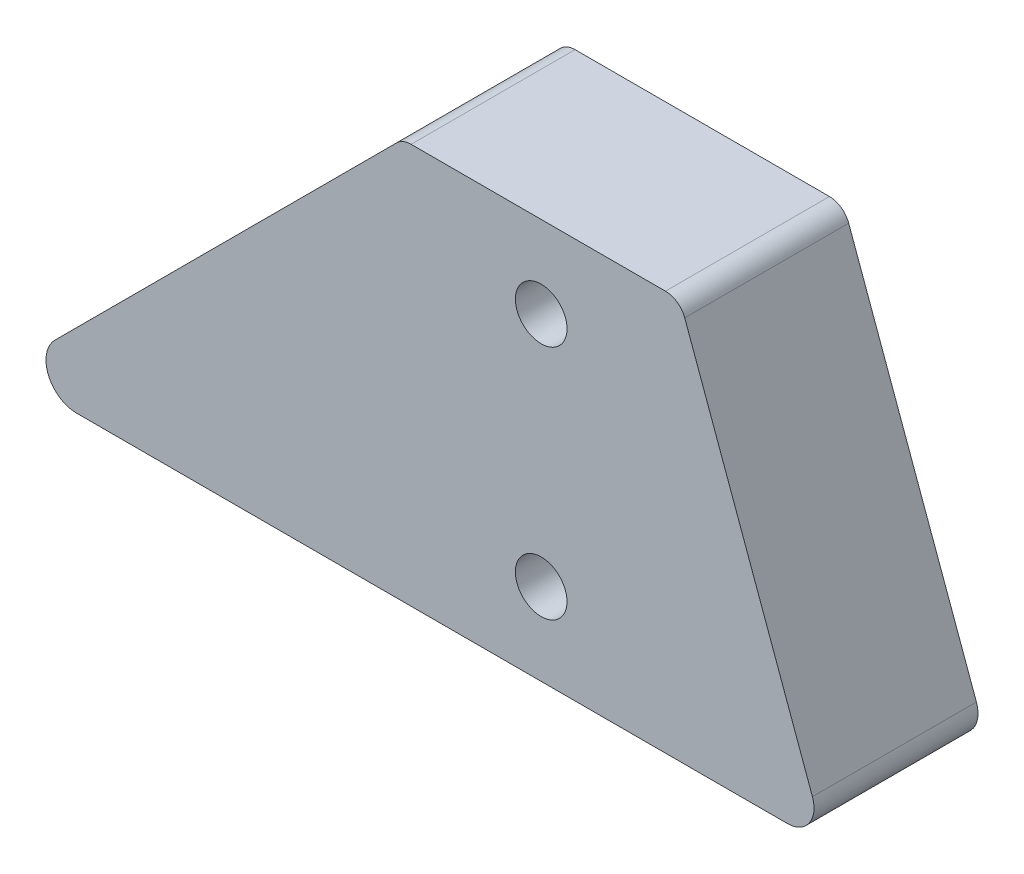
SolidWorks part; units mm, degrees
material "6061 Alloy"
ref_plane "Front Plane" through (0, 0, 0) normal (0, 0, 1) x (1, 0, 0)
ref_plane "Top Plane" through (0, 0, 0) normal (0, 1, 0) x (1, 0, 0)
ref_plane "Right Plane" through (0, 0, 0) normal (1, 0, 0) x (0, 0, -1)
sketch "Sketch1" plane through (0, 0, 0) normal (0, 0, 1) x (1, 0, 0)
  line L3 (9.525, 52.6) -> (-38.1, 52.6)
  line L5 (-38.1, 52.6) -> (-38.1, -45)
  line L6 (-38.1, -45) -> (9.525, -45)
  line L7 (9.525, 52.6) -> (9.525, -45)
  line L8 (-38.1, 52.6) -> (-46.0289, 52.6)
  line L9 (-49.5645, 51.1355) -> (-132.8967, -32.1967)
  line L10 (-127.5934, -45) -> (-38.1, -45)
  line L11 (9.525, 52.6) -> (16.024, 52.6)
  line L12 (20.7224, 49.3101) -> (51.8735, -36.2769)
  line L13 (45.7655, -45) -> (9.525, -45)
  line L14 (0, 0) -> (0, -25)
  line L15 (0, -25) -> (-14.2875, -25)
  line L16 (-14.2875, -45) -> (-14.2875, -25)
  line L17 (-14.2875, -25) -> (-14.2875, 32.625)
  arc A2 (-46.0289, 52.6) -> (-49.5645, 51.1355) centre (-46.0289, 47.6) ccw
  arc A3 (20.7224, 49.3101) -> (16.024, 52.6) centre (16.024, 47.6) ccw
  arc A4 (-127.5934, -45) -> (-132.8967, -32.1967) centre (-127.5934, -37.5) cw
  arc A5 (45.7655, -45) -> (51.8735, -36.2769) centre (45.7655, -38.5) ccw
  circle A6 centre (-14.2875, -25) radius 6.3
  circle A7 centre (-14.2875, 32.625) radius 6.3
  point P16 (-48.1, 52.6)
  point P19 (19.525, 52.6)
  dimension "D3" = 57.625
  dimension "D4" = 25
  dimension "D11" = 5
  dimension "D12" = 5
  dimension "D13" = 7.5
  dimension "D14" = 6.5
  dimension "D5" = 12.6
  dimension "D6" = 47.625
  dimension "D16" = 12.6
  dimension "D2" = 97.6
  dimension "D7" = 10
  dimension "D8" = 45
  dimension "D9" = 10
  dimension "D10" = 70
  dimension "D15" = 14.2875
  dimension "D17" = 20
extrude "Boss-Extrude1" add sketch "Sketch1" along normal blind 20 and the other way blind 20 contours L13 A5 L12 A3 L11 L7 | A7 A6 L6 L7 L3 L5 | A4 L10 L5 L8 A2 L9 region at (8.439, 3.8, 0) region at (25.1078, -6.3885, 0) region at (-73.4749, -9.314, 0)
